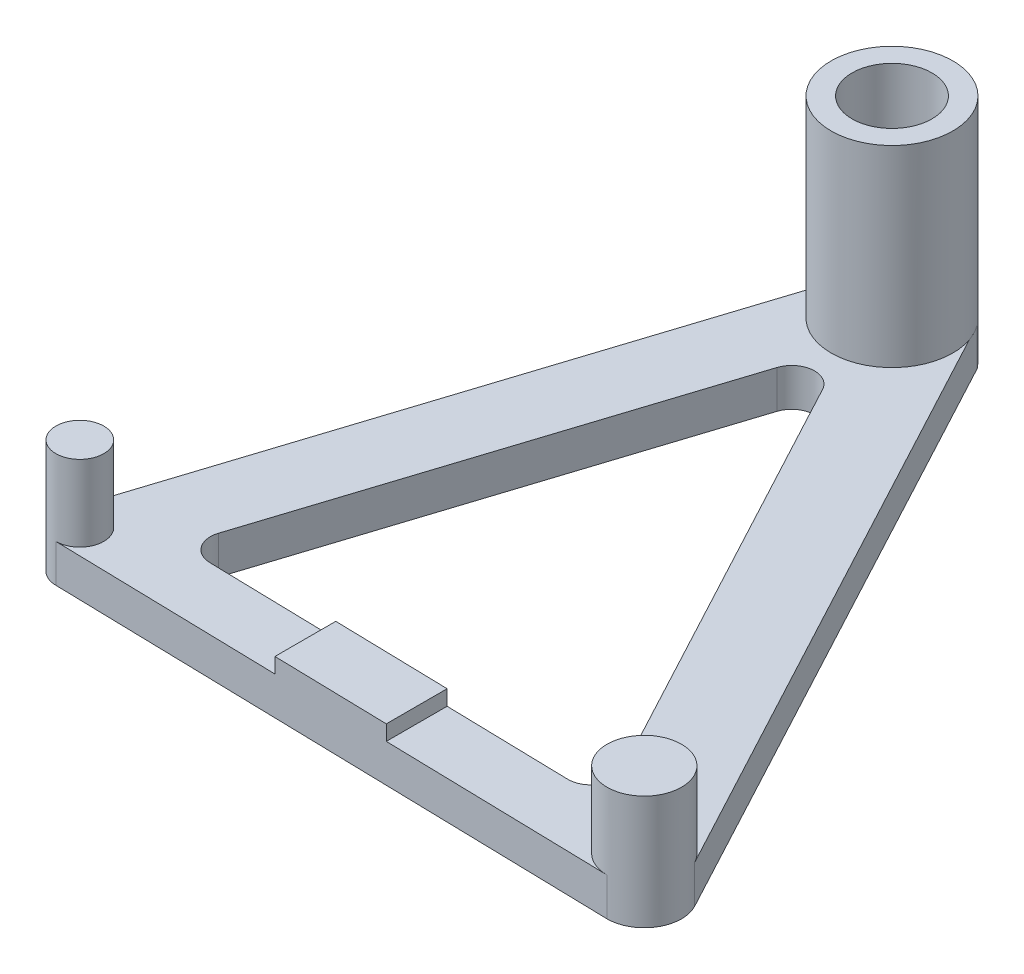
SolidWorks part; units mm, degrees
ref_plane "Front Plane" through (0, 0, 0) normal (0, 0, 1) x (1, 0, 0)
ref_plane "Top Plane" through (0, 0, 0) normal (0, 1, 0) x (1, 0, 0)
ref_plane "Right Plane" through (0, 0, 0) normal (1, 0, 0) x (0, 0, -1)
sketch "Эскиз1" plane through (0, 0, 0) normal (0, 1, 0) x (1, 0, 0)
  line L0 (0, 0) -> (-29.5363, -77.2992) construction
  line L1 (-29.5363, -77.2992) -> (44.7137, -77.2992) construction
  line L2 (44.7137, -77.2992) -> (0, 0) construction
  circle A0 centre (0, 0) radius 55 construction
  circle A1 centre (44.7137, -77.2992) radius 4.9
  circle A2 centre (-29.5363, -77.2992) radius 3.15
  circle A3 centre (0, 0) radius 5.25
  circle A4 centre (0, 0) radius 8
  dimension "D1" = 110
  dimension "D3" = 9.8
  dimension "D4" = 6.3
  dimension "D7" = 10.5
  dimension "D8" = 16
  dimension "D2" = 74.25
  dimension "D5" = 82.75
  dimension "D6" = 89.3
extrude "Бобышка-Вытянуть1" add sketch "Эскиз1" along normal blind 25.3
sketch "Эскиз2" plane through (0, 0, 0) normal (0, -1, 0) x (1, 0, 0)
  line L3 (-29.5363, 80.4492) -> (44.7137, 82.1992)
  line L4 (49.0352, 74.9895) -> (6.3674, -4.8432)
  line L5 (-32.5356, 76.3366) -> (-7.9993, -0.1095)
  circle A1 centre (-29.5363, 77.2992) radius 3.15 construction
  circle A2 centre (44.7137, 77.2992) radius 4.9 construction
  circle A3 centre (0, 0) radius 8 construction
  arc A4 (-7.9993, -0.1095) -> (6.3674, -4.8432) centre (0, 0) ccw
  arc A5 (49.0352, 74.9895) -> (44.4829, 82.1938) centre (44.7137, 77.2992) ccw
  arc A6 (-29.5363, 80.4492) -> (-32.5356, 76.3366) centre (-29.5363, 77.2992) ccw
  circle M1 centre (-29.5363, 77.2992) radius 3.15
extrude "Бобышка-Вытянуть2" add sketch "Эскиз2" along normal blind 5 contours L4 A5 L3 L5 A4 M1 | M1
sketch "Эскиз3" plane through (0, 25.3, 0) normal (0, 1, 0) x (1, 0, 0)
  line L1 (61.3743, -107.5125) -> (-40.0037, -107.5125)
  line L2 (61.3743, -107.5125) -> (61.3743, -49.9733)
  line L3 (61.3743, -49.9733) -> (-40.0037, -49.9733)
  line L4 (-40.0037, -107.5125) -> (-40.0037, -49.9733)
extrude "Вырез-Вытянуть1" cut sketch "Эскиз3" against normal offset from surface (15.3 mm away) 10 up to face at (0.301, 0, 52.1813)
sketch "Эскиз4" plane through (0, 0, 0) normal (0, 1, 0) x (1, 0, 0)
  line L0 (36.3309, -73.9972) -> (-21.0071, -72.6458)
  line L1 (-21.0071, -72.6458) -> (0.2355, -6.4617)
  line L2 (0.2355, -6.4617) -> (36.3309, -73.9972)
  line L3 (-29.5363, -80.4492) -> (44.4829, -82.1938) construction
  line L4 (-32.5356, -76.3366) -> (-7.9993, 0.1095) construction
  line L5 (49.0352, -74.9895) -> (7.5647, 2.603) construction
  line L6 (7.4733, -81.3215) -> (7.6619, -73.3215) construction
  point P14 (7.6619, -73.3215)
  dimension "D1" = 8
extrude "Вырез-Вытянуть2" cut sketch "Эскиз4" against normal through all
fillet "Скругление1" radius 3 3 edges at (0.2355, -2.5, 6.4617) (36.3309, -2.5, 73.9972) (-21.0071, -2.5, 72.6458)
sketch "Эскиз5" plane through (0, 0, 0) normal (0, 1, 0) x (1, 0, 0)
  circle A0 centre (0, 0) radius 5.25 construction
  circle A1 centre (0, 0) radius 5.25
extrude "Вырез-Вытянуть3" cut sketch "Эскиз5" against normal through all
sketch "Эскиз6" plane through (0, 0, 0) normal (0, 1, 0) x (1, 0, 0)
  line L0 (-0.0267, -73.1403) -> (-0.0267, -81.1447)
  line L1 (-16.9948, -72.7404) -> (31.1909, -73.8761) construction
  line L2 (-29.5363, -80.4492) -> (44.4829, -82.1938) construction
  line L3 (-0.0267, -81.1447) -> (14.9733, -81.4983)
  line L4 (14.9733, -81.4983) -> (14.9733, -73.4938)
  line L5 (14.9733, -73.4938) -> (-0.0267, -73.1403)
  line L6 (7.4733, -73.3171) -> (7.4733, -81.3215) construction
  dimension "D1" = 15
extrude "Бобышка-Вытянуть3" add sketch "Эскиз6" along normal blind 2
